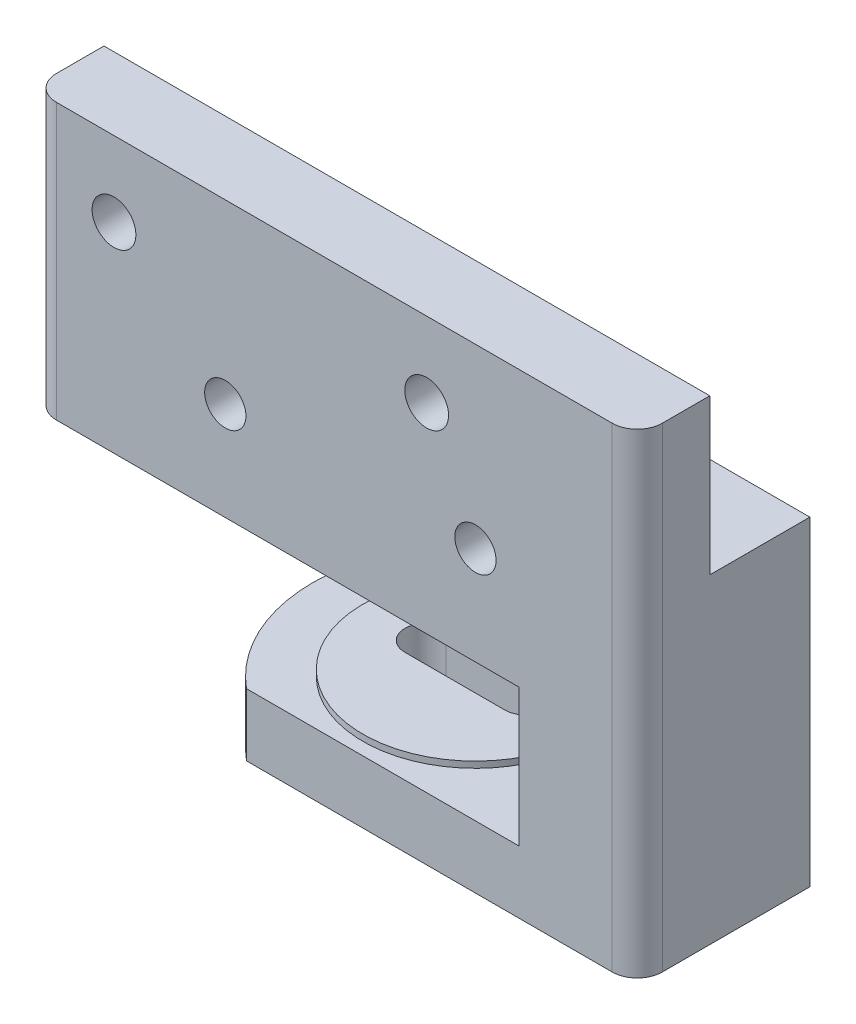
SolidWorks part; units mm, degrees
ref_plane "Front Plane" through (0, 0, 0) normal (0, 0, 1) x (1, 0, 0)
ref_plane "Top Plane" through (0, 0, 0) normal (0, 1, 0) x (1, 0, 0)
ref_plane "Right Plane" through (0, 0, 0) normal (1, 0, 0) x (0, 0, -1)
sketch "Croquis2" plane through (0, 0, 0) normal (0, 0, 1) x (1, 0, 0)
  line L0 (-13.2139, 0) -> (-13.2139, -8.55) construction
  line L1 (-61.65, -21.1) -> (-13.2139, -21.1)
  line L6 (-61.65, -21.1) -> (-61.65, -30.7)
  line L7 (-45.15, -31.7) -> (-27.15, -31.7) construction
  line L8 (-45.15, -31.7) -> (-27.15, -31.7) construction
  line L10 (-61.65, -21.1) -> (-13.2139, -21.1) construction
  line L11 (-61.65, -8.55) -> (-61.65, -30.7) construction
  line L12 (-390.05, -20.7) -> (-20.05, -20.7) construction
  line L13 (-13.2139, -21.1) -> (-13.2139, -30.7)
  line L14 (-61.65, -30.7) -> (-13.2139, -30.7)
  line L21 (-61.65, -30.7) -> (-13.2139, -30.7) construction
  point P8 (0, 0)
  point P12 (-52.65, -27.2)
  point P13 (0, 0)
  point P15 (-52.65, -27.2)
  point P18 (0, 0)
  dimension "D2" = 0.4
extrude "Saliente-Extruir2" add sketch "Croquis2" along normal offset from surface (13.8 mm away) 6 from offset 0.2 offset beyond the face yes
sketch "Croquis3" plane through (0, -30.7, 0) normal (0, -1, 0) x (1, 0, 0)
  line L0 (-13.2139, 14) -> (-13.2139, 0.2) construction
  line L1 (-61.65, 14) -> (-13.2139, 14)
  line L2 (-61.65, 14) -> (-61.65, 8.2)
  line L3 (-61.65, 8.2) -> (-13.2139, 8.2)
  line L4 (-13.2139, 14) -> (-13.2139, 8.2)
  line L6 (-390.05, 8) -> (-20.05, 8) construction
  circle A0 centre (-36.15, 4) radius 9 construction
  circle A1 centre (-36.15, 4) radius 9
  line M2 (-13.2139, 0.2) -> (-13.2139, 14)
  line M3 (-13.2139, 14) -> (-61.65, 14)
  dimension "D1" = 0.2
extrude "Saliente-Extruir3" add sketch "Croquis3" against normal up to surface (22 mm away) contours A1 L3 M2 M3 | L3 A1 region at (-37.432, -30.7, 13.5122) region at (-36.15, -30.7, 10.172)
sketch "Croquis4" plane through (0, -30.7, 0) normal (0, -1, 0) x (1, 0, 0)
  line L0 (-13.2139, 14) -> (-61.65, 14) construction
  line L1 (-13.2139, 14) -> (-61.65, 14)
  line L2 (-61.65, 0.2) -> (-13.2139, 0.2) construction
  line L3 (-61.65, 0.2) -> (-13.2139, 0.2)
  circle A0 centre (-36.15, 4) radius 9 construction
  circle A1 centre (-36.15, 4) radius 9
extrude "Saliente-Extruir5" add sketch "Croquis4" along normal blind 0.6 contours L1 A1 L3 region at (-36.15, -30.7, 5.8705)
sketch "Croquis6" plane through (-13.2139, 0, 0) normal (1, 0, 0) x (0, 0, -1)
  line L6 (-0.2, -21.1) -> (-8.2, -21.1)
  line L8 (-8.2, -8.7) -> (-14, -8.7)
  line L9 (-14, -8.7) -> (-14, -30.7)
  line L10 (-14, -30.7) -> (-0.2, -30.7)
  line L11 (-0.2, -30.7) -> (-0.2, -21.1)
  line L14 (-8.2, -8.7) -> (-14, -8.7)
  line L15 (-14, -8.7) -> (-14, -30.7)
  line L17 (-0.2, -30.7) -> (-0.2, -21.1)
  line L20 (-0.2, -21.1) -> (-8.2, -21.1)
  line L22 (-8.2, -21.1) -> (-8.2, -8.7)
  line L23 (-8.2, -21.1) -> (-8.2, -8.7)
  line L27 (-14, -30.7) -> (-0.2, -30.7)
  dimension "D1" = 0
sketch "Croquis5" plane through (0, 0, 14) normal (0, 0, 1) x (1, 0, 0)
  circle A0 centre (-30.05, -14.7) radius 1.75 construction
  circle A1 centre (-30.05, -14.7) radius 1.75
  circle A2 centre (-55.05, -14.7) radius 1.75 construction
  circle A3 centre (-55.05, -14.7) radius 1.75
  circle A4 centre (-46.15, -22.85) radius 1.65 construction
  circle A5 centre (-46.15, -22.85) radius 1.65
  circle A6 centre (-26.15, -22.85) radius 1.65 construction
  circle A7 centre (-26.15, -22.85) radius 1.65
extrude "Cortar-Extruir1" cut sketch "Croquis5" against normal up to next
sketch "Croquis7" plane through (0, -30.7, 0) normal (0, -1, 0) x (1, 0, 0)
  line L1 (-40.15, 4) -> (-32.15, 4) construction
  line L2 (-40.15, 5.65) -> (-32.15, 5.65)
  line L9 (-40.15, 2.35) -> (-32.15, 2.35)
  line L10 (-43.6171, 4) -> (-28.6829, 4) construction
  line L11 (-41.885, 7) -> (-43.6171, 4)
  line L12 (-43.6171, 4) -> (-41.885, 1)
  line L13 (-41.885, 1) -> (-30.415, 1)
  line L14 (-30.415, 1) -> (-28.6829, 4)
  line L15 (-28.6829, 4) -> (-30.415, 7)
  line L16 (-30.415, 7) -> (-41.885, 7)
  circle A1 centre (-36.15, 4) radius 2.5 construction
  circle A2 centre (-36.15, 4) radius 2.5 construction
  arc A3 (-40.15, 5.65) -> (-40.15, 2.35) centre (-40.15, 4) ccw
  arc A4 (-32.15, 2.35) -> (-32.15, 5.65) centre (-32.15, 4) ccw
  point P5 (-36.15, 4)
  point P10 (-36.15, 4)
  point P18 (-36.15, 4)
  dimension "D1" = 1.65
  dimension "D2" = 8
  dimension "D3" = 3.4641
  dimension "D4" = 11.47
  dimension "D5" = 120
  dimension "D6" = 120
  dimension "D7" = 120
  dimension "D8" = 120
extrude "Cortar-Extruir2" cut sketch "Croquis7" along normal blind 2.6 and the other way blind 3.5 from surface contours L15 L16 L11 L12 L13 L14 A4 L9 A3 L2 region at (-36.15, -30.7, 6.8391) starting at face at (-37.432, -21.1, 4.2)
sketch "Croquis8" plane through (0, -30.7, 0) normal (0, -1, 0) x (1, 0, 0)
  line L9 (-27.9916, 0.2) -> (-13.2139, 0.2) construction
  line L10 (-13.2139, 14) -> (-22.65, 14)
  line L11 (-13.2139, 14) -> (-13.2139, 0.2)
  line L12 (-13.2139, 0.2) -> (-22.65, 0.2)
  line L13 (-22.65, 14) -> (-22.65, 0.2)
  circle A3 centre (-36.15, 4) radius 9 construction
  line M7 (-27.9916, 0.2) -> (-13.2139, 0.2)
  line M10 (-13.2139, 14) -> (-61.65, 14)
  line M34 (-13.2139, 0.2) -> (-13.2139, 14)
  dimension "D1" = 4.5
extrude "Saliente-Extruir7" add sketch "Croquis8" along normal offset from surface (11 mm away) 1 contours L13 M10 M7 M34 region at (-17.932, -30.7, 7.1) offset beyond the face yes
sketch "Croquis9" plane through (0, -41.7, 0) normal (0, -1, 0) x (1, 0, 0)
  line L1 (-13.2139, 14) -> (-13.2139, 0.2) construction
  line L2 (-40.15, 2.35) -> (-32.15, 2.35) construction
  line L3 (-61.65, 14) -> (-61.65, 0.2) construction
  line L8 (-61.65, 14) -> (-61.65, -20.4633) construction
  line L12 (-13.2139, 14) -> (-61.65, 14)
  line L15 (-13.2139, 14) -> (-13.2139, -6)
  line L16 (-40.15, 5.65) -> (-32.15, 5.65) construction
  line L17 (-40.15, 2.35) -> (-32.15, 2.35)
  line L18 (-40.15, 5.65) -> (-32.15, 5.65)
  line L19 (-13.2139, -6) -> (-61.65, -6)
  line L20 (-61.65, 14) -> (-61.65, -6)
  circle A0 centre (-36.15, 4) radius 9
  arc A2 (-40.15, 5.65) -> (-40.15, 2.35) centre (-40.15, 4) ccw construction
  arc A4 (-40.15, 5.65) -> (-40.15, 2.35) centre (-40.15, 4) ccw
  arc A5 (-32.15, 2.35) -> (-32.15, 5.65) centre (-32.15, 4) ccw construction
  arc A6 (-32.15, 2.35) -> (-32.15, 5.65) centre (-32.15, 4) ccw
  circle A7 centre (-36.15, 4) radius 9 construction
  point P17 (-45.15, 10.8)
  line M50 (-13.2139, 14) -> (-22.65, 14)
  line M52 (-22.65, 14) -> (-22.65, 0.2)
  line M61 (-22.65, 0.2) -> (-13.2139, 0.2)
  line M63 (-13.2139, 0.2) -> (-13.2139, 14)
  dimension "D2" = 1
extrude "Saliente-Extruir8" add sketch "Croquis9" along normal blind 5 contours M50 M52 M61 M63 | L12 L20 L19 L15 A6 L17 A4 L18 region at (-17.932, -41.7, 7.1) region at (-23.174, -41.7, 7.1)
extrude "Cortar-Extruir3" cut sketch "Croquis7<3>" along normal through all and the other way up to surface (9.6 mm away) contours L9 A4 L2 A3 region at (-36.15, -30.7, 4) other way up to face at (-36.15, -21.1, 4)
sketch "Croquis7<3>" plane through (0, -30.7, 0) normal (0, -1, 0) x (1, 0, 0) same geometry as "Croquis7"
extrude "Saliente-Extruir9" add sketch "Croquis9<3>" against normal blind 0.5 contours A0 A6 L17 A4 L18 region at (-44.8954, -41.7, 4)
sketch "Croquis9<3>" plane through (0, -41.7, 0) normal (0, -1, 0) x (1, 0, 0) same geometry as "Croquis9"
extrude "Saliente-Extruir10" add sketch "Croquis9<4>" along normal up to surface (5 mm away) contours A0 A6 L17 A4 L18 region at (-44.8954, -41.7, 4) up to face at (-37.432, -46.7, 4)
sketch "Croquis9<4>" plane through (0, -41.7, 0) normal (0, -1, 0) x (1, 0, 0) same geometry as "Croquis9"
sketch "Croquis10" plane through (0, -41.7, 0) normal (0, 1, 0) x (1, 0, 0)
  line L1 (-13.2139, 6) -> (-22.65, 6)
  line L2 (-13.2139, 6) -> (-13.2139, -0.2)
  line L3 (-13.2139, -0.2) -> (-22.65, -0.2)
  line L4 (-22.65, 6) -> (-22.65, -0.2)
extrude "Cortar-Extruir4" cut sketch "Croquis10" against normal blind 10
sketch "Croquis11" plane through (0, -41.7, 0) normal (0, 1, 0) x (1, 0, 0)
  line L0 (-61.65, -14) -> (-44.4566, -14)
  line L1 (-22.65, -14) -> (-61.65, -14) construction
  line L2 (-61.65, -14) -> (-61.65, 6)
  line L3 (-61.65, 6) -> (-43.0004, 7.0486)
  line L4 (-22.65, 6) -> (-27.8434, 6)
  line L7 (-22.65, 6) -> (-22.65, -0.2)
  line L8 (-22.65, -0.2) -> (-23.7178, -0.2)
  arc A2 (-23.15, -4) -> (-23.15, -4) centre (-36.15, -4) ccw
  circle A3 centre (-36.15, -4) radius 13
  line M5 (-22.65, 6) -> (-61.65, 6)
  line M6 (-61.65, 6) -> (-61.65, -14)
  line M7 (-61.65, -14) -> (-22.65, -14)
  line M13 (-22.65, -0.2) -> (-22.65, 6)
  dimension "D1" = 4
extrude "Cortar-Extruir5" cut sketch "Croquis11" against normal blind 10 contours A3 M5 M6 M7 | A3 L8 M13 M5 region at (-54.6195, -41.7, 4) region at (-24.2536, -41.7, -3.672)
fillet "Redondeo2" radius 2 1 edges at (-61.65, -19.7, 14)
fillet "Redondeo3" radius 2 1 edges at (-13.2139, -27.7, 14)
